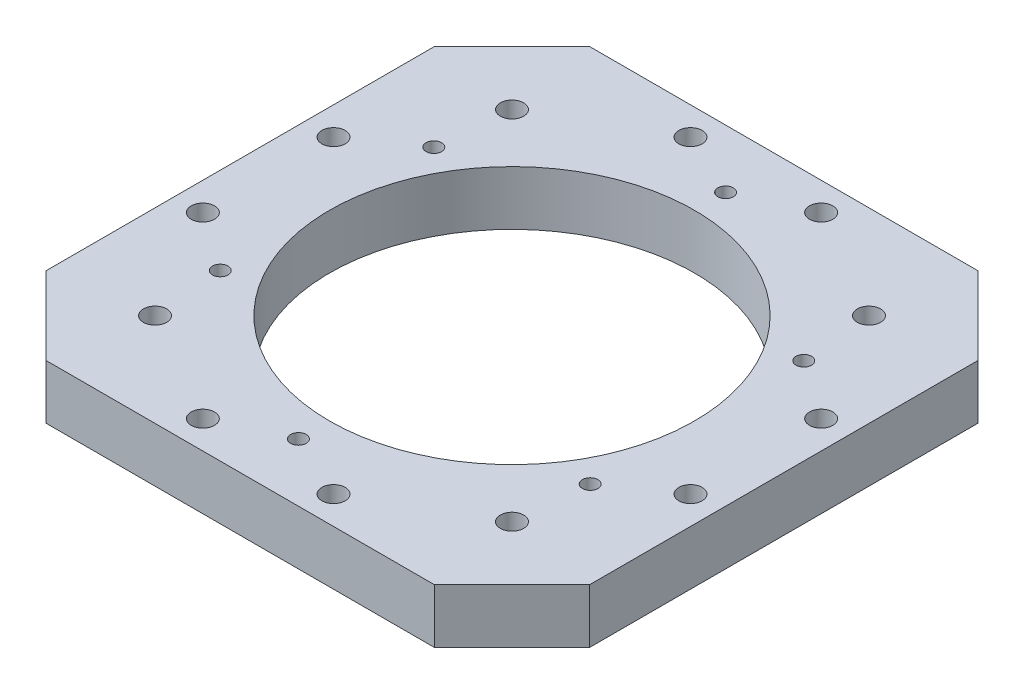
SolidWorks part; units mm, degrees
ref_plane "Front Plane" through (0, 0, 0) normal (0, 0, 1) x (1, 0, 0)
ref_plane "Top Plane" through (0, 0, 0) normal (0, 1, 0) x (1, 0, 0)
ref_plane "Right Plane" through (0, 0, 0) normal (1, 0, 0) x (0, 0, -1)
sketch "Sketch1" plane through (0, 0, 0) normal (0, 1, 0) x (1, 0, 0)
  line L0 (-53.2191, 0) -> (0, 0) construction
  line L1 (0, 0) -> (-55.1529, -14.7782) construction
  line L2 (-35, 35) -> (35, 35)
  line L3 (-35, 35) -> (-35, -35)
  line L4 (35, 35) -> (35, -35)
  line L5 (-35, -35) -> (35, -35)
  circle A0 centre (0, 0) radius 35 construction
  circle A1 centre (0, 0) radius 27.5 construction
  circle A2 centre (0, 0) radius 23.5
  circle A3 centre (0, 27.5) radius 1
  circle A4 centre (23.8157, 13.75) radius 1
  circle A5 centre (23.8157, -13.75) radius 1
  circle A6 centre (0, -27.5) radius 1
  circle A7 centre (-23.8157, -13.75) radius 1
  circle A8 centre (-23.8157, 13.75) radius 1
  circle A9 centre (0, 0) radius 32.5 construction
  circle A10 centre (-31.3926, -8.4116) radius 1.5
  circle A11 centre (-31.3926, 8.4116) radius 1.5
  circle A12 centre (-22.981, 22.981) radius 1.5
  circle A13 centre (-8.4116, 31.3926) radius 1.5
  circle A14 centre (8.4116, 31.3926) radius 1.5
  circle A15 centre (22.981, 22.981) radius 1.5
  circle A16 centre (31.3926, 8.4116) radius 1.5
  circle A17 centre (31.3926, -8.4116) radius 1.5
  circle A18 centre (22.981, -22.981) radius 1.5
  circle A19 centre (8.4116, -31.3926) radius 1.5
  circle A20 centre (-8.4116, -31.3926) radius 1.5
  circle A21 centre (-22.981, -22.981) radius 1.5
  point P19 (0, 0)
  point P47 (0, 0)
  dimension "D1" = 70
  dimension "D2" = 47
  dimension "D3" = 55
  dimension "D4" = 2
  dimension "D7" = 65
  dimension "D8" = 3
  dimension "D6" = 15
  dimension "D5" = 6
  dimension "D9" = 12
extrude "Boss-Extrude1" add sketch "Sketch1" along normal blind 7
chamfer "Chamfer1" distance 10 angle 45 4 edges at (-35, 3.5, 35) (35, 3.5, 35) (35, 3.5, -35) (-35, 3.5, -35)
